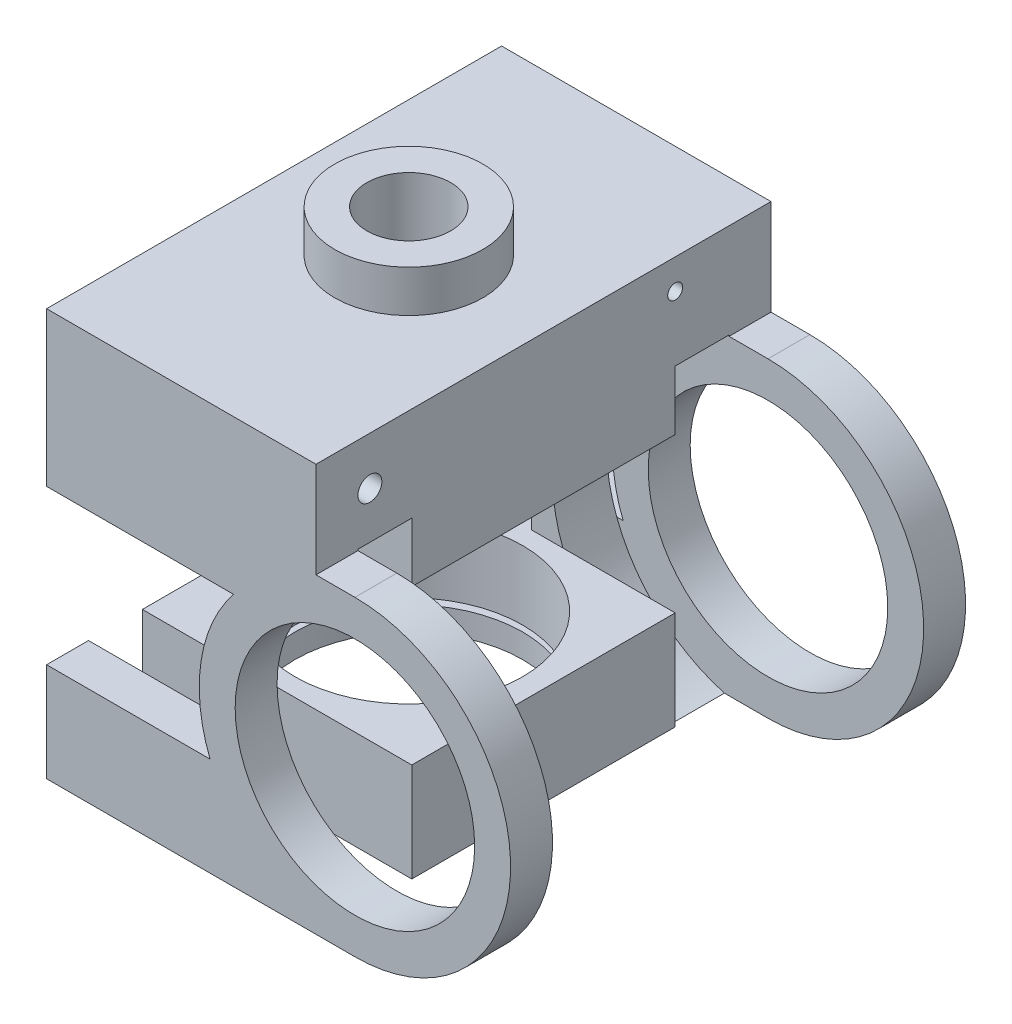
SolidWorks part; units mm, degrees
ref_plane "Plan de face" through (0, 0, 0) normal (0, 0, 1) x (1, 0, 0)
ref_plane "Plan de dessus" through (0, 0, 0) normal (0, 1, 0) x (1, 0, 0)
ref_plane "Plan de droite" through (0, 0, 0) normal (1, 0, 0) x (0, 0, -1)
sketch "Sketch4" plane through (0, 0, 0) normal (0, 0, 1) x (1, 0, 0)
  line L0 (0, 13) -> (-3.25, 13)
  line L1 (-3.25, 13) -> (-3.25, 21)
  line L2 (-3.25, 21) -> (-25.75, 21)
  line L3 (-25.75, 21) -> (-25.75, 8.15)
  line L4 (-25.75, 8.15) -> (-10.1281, 8.15)
  line L5 (0, -13) -> (-25.75, -13)
  line L6 (-25.75, -13) -> (-25.75, -4.75)
  line L7 (-25.75, -4.75) -> (-12.1011, -4.75)
  circle A0 centre (0, 0) radius 10
  arc A1 (-10.1281, 8.15) -> (-12.1011, -4.75) centre (0, 0) ccw
  arc A2 (0, -13) -> (0, 13) centre (0, 0) ccw
  dimension "D1" = 20
  dimension "D2" = 26
  dimension "D3" = 3.25
  dimension "D4" = 8
  dimension "D5" = 22.5
  dimension "D6" = 12.85
  dimension "D7" = 25.75
  dimension "D8" = 8.25
extrude "Boss-Extrude4" add sketch "Sketch4" along normal blind 3.5
sketch "Sketch5" plane through (0, 0, 3.5) normal (0, 0, 1) x (1, 0, 0)
  line L0 (-15.25, 8.15) -> (-25.75, 8.15)
  line L2 (-25.75, 8.15) -> (-25.75, 21)
  line L3 (-25.75, 21) -> (-3.25, 21)
  line L4 (-3.25, 21) -> (-3.25, 13.103)
  line L5 (-25.75, -4.75) -> (-15.25, -4.75)
  line L6 (-12.1011, -4.75) -> (-25.75, -4.75) construction
  line L7 (-25.75, -4.75) -> (-25.75, -13) construction
  line L9 (-25.75, -4.75) -> (-25.75, -13)
  line L10 (-25.75, -13) -> (-3.6401, -13)
  line L11 (-25.75, -13) -> (0, -13) construction
  line L12 (-15.25, 8.15) -> (-15.25, -4.75)
  arc A3 (-3.25, 13.103) -> (-3.6401, -13) centre (0, 0) ccw
  dimension "D1" = 27
  dimension "D2" = 15.25
extrude "Boss-Extrude5" add sketch "Sketch5" along normal blind 4.5
sketch "Sketch6" plane through (0, 0, 8) normal (0, 0, 1) x (1, 0, 0)
  line L1 (-25.75, 21) -> (-3.25, 21)
  line L2 (-25.75, 21) -> (-25.75, 8.15)
  line L3 (-25.75, 8.15) -> (-3.25, 8.15)
  line L4 (-3.25, 21) -> (-3.25, 8.15)
  line L5 (-25.75, -13) -> (-3.25, -13)
  line L6 (-25.75, -13) -> (-25.75, -4.75)
  line L7 (-25.75, -4.75) -> (-3.25, -4.75)
  line L8 (-3.25, -13) -> (-3.25, -4.75)
  dimension "D1" = 22.5
  dimension "D2" = 12.9
extrude "Boss-Extrude6" add sketch "Sketch6" along normal blind 22
sketch "Sketch7" plane through (0, 0, 30) normal (0, 0, 1) x (1, 0, 0)
  line L1 (-25.75, 21) -> (-3.25, 21)
  line L2 (-25.75, 21) -> (-25.75, 8.15)
  line L3 (-25.75, 8.15) -> (-10.7623, 8.15)
  line L4 (-3.25, 21) -> (-3.25, 13.103)
  arc A0 (-3.25, 13.103) -> (-10.7623, 8.15) centre (0, 0) ccw
  dimension "D1" = 27
extrude "Boss-Extrude7" add sketch "Sketch7" along normal blind 4.5
sketch "Sketch8" plane through (0, 0, 34.5) normal (0, 0, 1) x (1, 0, 0)
  line L0 (0, 13) -> (-3.25, 13)
  line L3 (-3.25, 13) -> (-3.25, 21)
  line L4 (-3.25, 21) -> (-25.75, 21)
  line L5 (-25.75, 21) -> (-25.75, 8.15)
  line L6 (-25.75, 8.15) -> (-10.1281, 8.15)
  line L7 (-12.1011, -4.75) -> (-25.75, -4.75)
  line L8 (-25.75, -4.75) -> (-25.75, -13)
  line L9 (-25.75, -13) -> (0, -13)
  arc A0 (-10.1281, 8.15) -> (-12.1011, -4.75) centre (0, 0) ccw
  circle A1 centre (0, 0) radius 10
  arc A2 (0, -13) -> (0, 13) centre (0, 0) ccw
  dimension "D1" = 3.25
  dimension "D2" = 20
  dimension "D3" = 25.75
extrude "Boss-Extrude8" add sketch "Sketch8" along normal blind 3.5
sketch "Sketch9" plane through (0, 21, 0) normal (0, 1, 0) x (1, 0, 0)
  line L0 (-3.25, -38) -> (-25.75, -38) construction
  line L1 (-3.25, -38) -> (-3.25, 0) construction
  circle A0 centre (-14.5, -19) radius 6.187
  dimension "D1" = 19
  dimension "D2" = 11.25
extrude "Boss-Extrude9" add sketch "Sketch9" along normal blind 3.5
sketch "Sketch10" plane through (0, 24.5, 0) normal (0, 1, 0) x (1, 0, 0)
  circle A0 centre (-14.5, -19) radius 3.5
  dimension "D1" = 7
extrude "Cut-Extrude1" cut sketch "Sketch10" against normal blind 9.5 contours A0
sketch "Sketch11" plane through (0, 15, 0) normal (0, 1, 0) x (1, 0, 0)
  circle A0 centre (-14.5, -19) radius 8.5
  dimension "D1" = 17
extrude "Cut-Extrude2" cut sketch "Sketch11" against normal blind 0.5
sketch "Sketch12" plane through (0, 14.5, 0) normal (0, 1, 0) x (1, 0, 0)
  circle A0 centre (-14.5, -19) radius 9.5
  dimension "D1" = 19
extrude "Cut-Extrude3" cut sketch "Sketch12" against normal up to next
sketch "Sketch13" plane through (0, -13, 0) normal (0, -1, 0) x (1, 0, 0)
  line L0 (-25.75, 30) -> (-25.75, 0) construction
  line L2 (-3.6401, 8) -> (-3.25, 8) construction
  circle A0 centre (-14.5, 19) radius 9.5
  dimension "D1" = 11.25
  dimension "D3" = 19
  dimension "D2" = 11
extrude "Cut-Extrude4" cut sketch "Sketch13" against normal blind 2
sketch "Sketch14" plane through (0, -11, 0) normal (0, -1, 0) x (1, 0, 0)
  circle A0 centre (-14.5, 19) radius 10.5
  dimension "D1" = 21
extrude "Cut-Extrude5" cut sketch "Sketch14" against normal blind 0.5
sketch "Sketch15" plane through (0, -10.5, 0) normal (0, -1, 0) x (1, 0, 0)
  circle A0 centre (-14.5, 19) radius 9.5
  dimension "D1" = 19
extrude "Cut-Extrude6" cut sketch "Sketch15" against normal blind 5.75
sketch "Sketch18" plane through (-3.25, 0, 0) normal (1, 0, 0) x (0, 0, -1)
  line L0 (0, 13) -> (0, 21) construction
  line L1 (-38, 21) -> (0, 21) construction
  point P0 (-8, 18.5)
  dimension "D1" = 8
  dimension "D2" = 2.5
hole_wizard "Tap Drill for M1.6 Tap1" positions "Sketch18" profile "Sketch17" hole size "M1.6" standard "ISO"
sketch "Sketch17" plane through (-3.25, 18.5, 8) normal (0, 1, 0) x (0, 0, -1)
  line L0 (0, 0) -> (0, 5.8755)
  line L1 (0, 5.8755) -> (0.625, 5.5)
  line L2 (0.625, 5.5) -> (0.625, 0)
  line L5 (0.625, 0) -> (0, 0)
  line L10 (0, 5.8755) -> (-0.625, 5.5) construction
  line L11 (0, -6.35) -> (0, 107.95) construction
  dimension "Hole Dia." = 1.25
  dimension "Hole Depth" = 5.5
  dimension "Drill Angle" = 118
cosmetic thread "Cosmetic Thread1" parameters "D1"=4.5, "D2"=2.2
sketch "Sketch21" plane through (-3.25, 0, 0) normal (1, 0, 0) x (0, 0, -1)
  line L0 (-38, 13) -> (-38, 21) construction
  line L1 (-38, 21) -> (0, 21) construction
  point P0 (-33.5, 17)
  dimension "D1" = 4.5
  dimension "D2" = 4
hole_wizard "Ø2.0 (2) Diameter Hole1" positions "Sketch21" profile "Sketch20" hole size "Ø2.0" standard "ISO" end condition through all
sketch "Sketch20" plane through (-3.25, 17, 33.5) normal (0, 1, 0) x (0, 0, -1)
  line L0 (0, 0) -> (0, 22.5)
  line L1 (0, 22.5) -> (1, 22.5)
  line L2 (1, 22.5) -> (1, 0)
  line L5 (1, 0) -> (0, 0)
  line L11 (0, -6.35) -> (0, 107.95) construction
  dimension "Thru Hole Dia." = 2
  dimension "Thru Hole Depth" = 22.5
